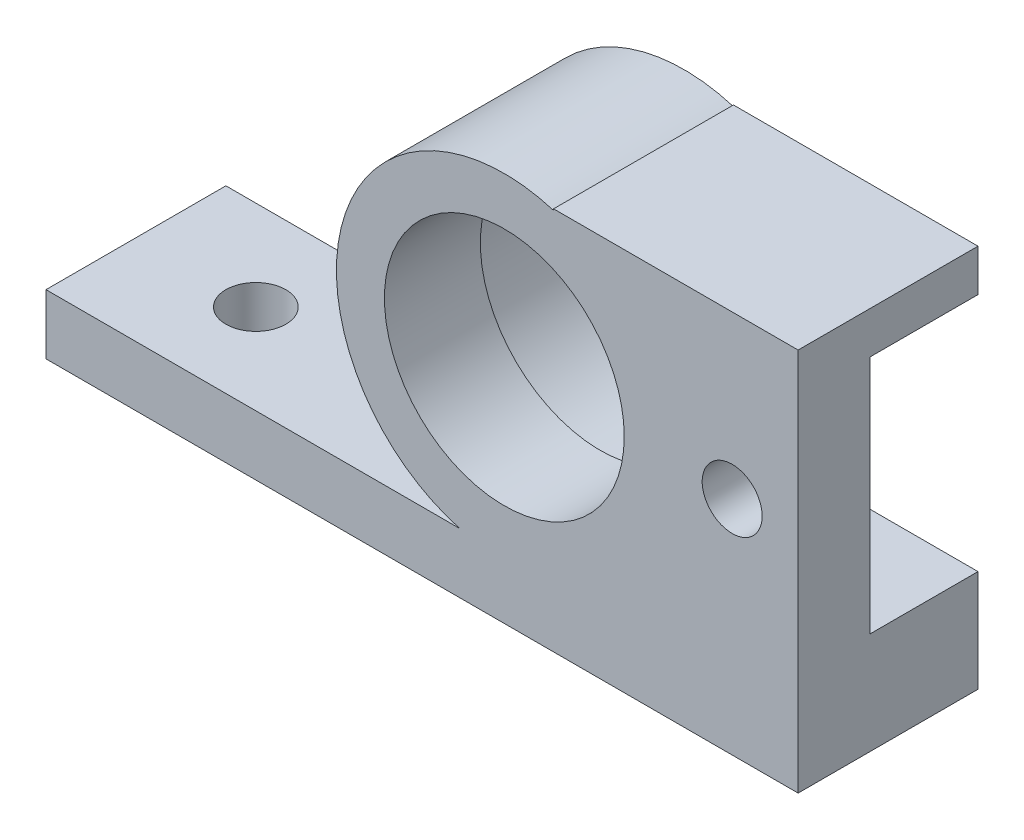
SolidWorks part; units mm, degrees
ref_plane "前视基准面" through (0, 0, 0) normal (0, 0, 1) x (1, 0, 0)
ref_plane "上视基准面" through (0, 0, 0) normal (0, 1, 0) x (1, 0, 0)
ref_plane "右视基准面" through (0, 0, 0) normal (1, 0, 0) x (0, 0, -1)
sketch "草图1" plane through (0, 0, 0) normal (0, 0, 1) x (1, 0, 0)
  line L1 (20, -10) -> (-20, -10)
  line L2 (20, -10) -> (20, 10)
  line L3 (20, 10) -> (-20, 10)
  line L4 (-20, -10) -> (-20, 10)
  line L5 (20, -10) -> (-20, 10) construction
  line L6 (20, 10) -> (-20, -10) construction
  point P0 (0, 0)
  dimension "D1" = 40
  dimension "D2" = 20
extrude "凸台-拉伸1" add sketch "草图1" along normal blind 6
sketch "草图2" plane through (0, 0, 6) normal (0, 0, 1) x (1, 0, 0)
  line L0 (20, -10) -> (20, 10) construction
  circle A0 centre (10, 0) radius 2.5
  circle A1 centre (-1, 0) radius 2.5
  circle A2 centre (-12, 0) radius 2.5
  dimension "D1" = 10
  dimension "D2" = 5
  dimension "D3" = 3
extrude "切除-拉伸1" cut sketch "草图2" against normal through all
sketch "草图3" plane through (0, 0, 6) normal (0, 0, 1) x (1, 0, 0)
  line L0 (20, 13.5) -> (20, 10)
  line L1 (20, -13.5) -> (-26.894, -13.5)
  line L3 (20, 13.5) -> (-26.894, 13.5)
  line L4 (-20, 10) -> (-20, -10)
  line L5 (-20, -10) -> (20, -10)
  line L6 (20, -10) -> (20, 10)
  line L7 (20, 10) -> (-20, 10)
  line L8 (-20, 10) -> (-20, -10)
  line L9 (-20, -10) -> (20, -10)
  line L10 (20, -10) -> (20, 10)
  line L11 (20, 10) -> (-20, 10)
  line L12 (-26.894, -13.5) -> (-26.894, 13.5)
  line L13 (20, -10.0394) -> (-26.894, 13.5) construction
  line L14 (20, 10.0394) -> (-26.894, -13.5) construction
  line L15 (20, -10) -> (20, -13.5)
  circle A0 centre (-31, 0) radius 11
  circle A1 centre (-31, 0) radius 14
  point P2 (0, 0)
  line M10 (-20, 10) -> (-20, -10)
  line M11 (-20, -10) -> (20, -10)
  line M13 (20, 10) -> (-20, 10)
  dimension "D3" = 22
  dimension "D4" = 28
  dimension "D2" = 3.5
  dimension "D1" = 0
extrude "凸台-拉伸2" add sketch "草图3" against normal blind 15 contours L3 A1 L1 L12 A0 | A1 L1 L15 M11 M10 | L1 A1 L8 A0 L12 | L8 A1 L3 L12 A0 | L8 A1 | A1 L0 L3 M10 M13 region at (-1.9449, 11.7771, 6) region at (-1.9449, -11.7771, 6) region at (-23.0173, 9.0328, 6) region at (-27.2274, 11.7946, 6) region at (-18.7882, 0, 6) region at (-23.0173, -9.0328, 6)
sketch "草图5" plane through (0, 0, 6) normal (0, 0, 1) x (1, 0, 0)
  circle A0 centre (-31, 0) radius 10
  circle A1 centre (-31, 0) radius 11 construction
  circle A2 centre (-31, 0) radius 11
  dimension "D1" = 20
extrude "凸台-拉伸3" add sketch "草图5" against normal blind 8
sketch "草图6" plane through (0, 0, 6) normal (0, 0, 1) x (1, 0, 0)
  circle A0 centre (-31, 0) radius 8.5
  circle A1 centre (-31, 0) radius 10 construction
  circle A2 centre (-31, 0) radius 10
  dimension "D1" = 17
sketch "草图8" plane through (0, 0, 6) normal (0, 0, 1) x (1, 0, 0)
  line L0 (20, -13.5) -> (20, 13.5) construction
  line L1 (20, -13.5) -> (-26.894, -13.5) construction
  line L2 (20, 13.5) -> (-26.894, 13.5) construction
  line L3 (20, -13.5) -> (20, 13.5)
  line L4 (20, -13.5) -> (-26.894, -13.5)
  line L5 (20, 13.5) -> (-26.894, 13.5)
  line L6 (-45, -14) -> (-26.894, -13.5)
  line L7 (-45, -14) -> (-239, -14)
  line L8 (-45, -14) -> (-45, 14)
  line L9 (-45, 14) -> (-239, 14)
  line L10 (-239, -14) -> (-239, 14)
  line L11 (-45, -14) -> (-239, 14) construction
  line L12 (-45, 14) -> (-239, -14) construction
  line L13 (-45, 14) -> (-26.894, 13.3843)
  line L14 (-12, 0) -> (-31, 0)
  arc A0 (-26.894, 13.3843) -> (-26.894, -13.3843) centre (-31, 0) ccw construction
  arc A1 (-26.894, 13.3843) -> (-26.894, -13.3843) centre (-31, 0) ccw
  point P6 (-142, 0)
  dimension "D1" = 28
  dimension "D2" = 194
  dimension "D3" = 14
sketch "草图9" plane through (0, -13.5, 0) normal (0, -1, 0) x (1, 0, 0)
  circle A0 centre (10.5344, 0) radius 5.2388
sketch "草图10" plane through (20, 0, 0) normal (1, 0, 0) x (0, 0, -1)
  line L1 (9, -13.5) -> (-6, -13.5)
  line L2 (9, -13.5) -> (9, -18.5)
  line L3 (9, -18.5) -> (-6, -18.5)
  line L4 (-6, -13.5) -> (-6, -18.5)
  dimension "D1" = 5
extrude "凸台-拉伸4" add sketch "草图10" against normal blind 500
sketch "草图11" plane through (0, 0, -9) normal (0, 0, -1) x (-1, 0, 0)
  line L1 (22.0371, -11.3638) -> (33.5283, -11.3638)
  line L2 (22.0371, -11.3638) -> (22.0371, -16.4864)
  line L3 (22.0371, -16.4864) -> (33.5283, -16.4864)
  line L4 (33.5283, -11.3638) -> (33.5283, -16.4864)
extrude "凸台-拉伸5" add sketch "草图11" against normal through all
sketch "草图12" plane through (0, 0, 6) normal (0, 0, 1) x (1, 0, 0)
  line L0 (-12, 0) -> (-1, 0) construction
  line L1 (-6.5, 0) -> (-6.5, 13.5) construction
  line L2 (20, 13.5) -> (-26.894, 13.5) construction
  line L4 (-6.5, 13.5) -> (20, 13.5)
  line L5 (-6.5, 13.5) -> (-6.5, -18.5)
  line L6 (-6.5, -18.5) -> (20, -18.5)
  line L7 (20, 13.5) -> (20, -18.5)
extrude "切除-拉伸2" cut sketch "草图12" against normal through all
sketch "草图13" plane through (0, -18.5, 0) normal (0, -1, 0) x (1, 0, 0)
  line L0 (-69.2198, 6) -> (-69.2198, -9.0491)
  line L1 (-480, 6) -> (-6.5, 6) construction
  line L2 (-69.2198, 131.4142) -> (-69.2198, -238.5858) construction
sketch "草图14" plane through (0, -18.5, 0) normal (0, -1, 0) x (1, 0, 0)
  line L1 (-69.2198, -9.0491) -> (-494.0275, -9.0491)
  line L2 (-69.2198, -9.0491) -> (-69.2198, 12.8124)
  line L3 (-69.2198, 12.8124) -> (-494.0275, 12.8124)
  line L4 (-494.0275, -9.0491) -> (-494.0275, 12.8124)
extrude "切除-拉伸3" cut sketch "草图14" against normal through all
sketch "草图15" plane through (0, -18.5, 0) normal (0, -1, 0) x (1, 0, 0)
  line L0 (-69.2198, 6) -> (-69.2198, -9) construction
  line L1 (-69.2198, -1.5) -> (-59.2198, -1.5) construction
  circle A0 centre (-59.2198, -1.5) radius 2.5
  dimension "D1" = 5
  dimension "D2" = 10
extrude "切除-拉伸4" cut sketch "草图15" against normal through all
